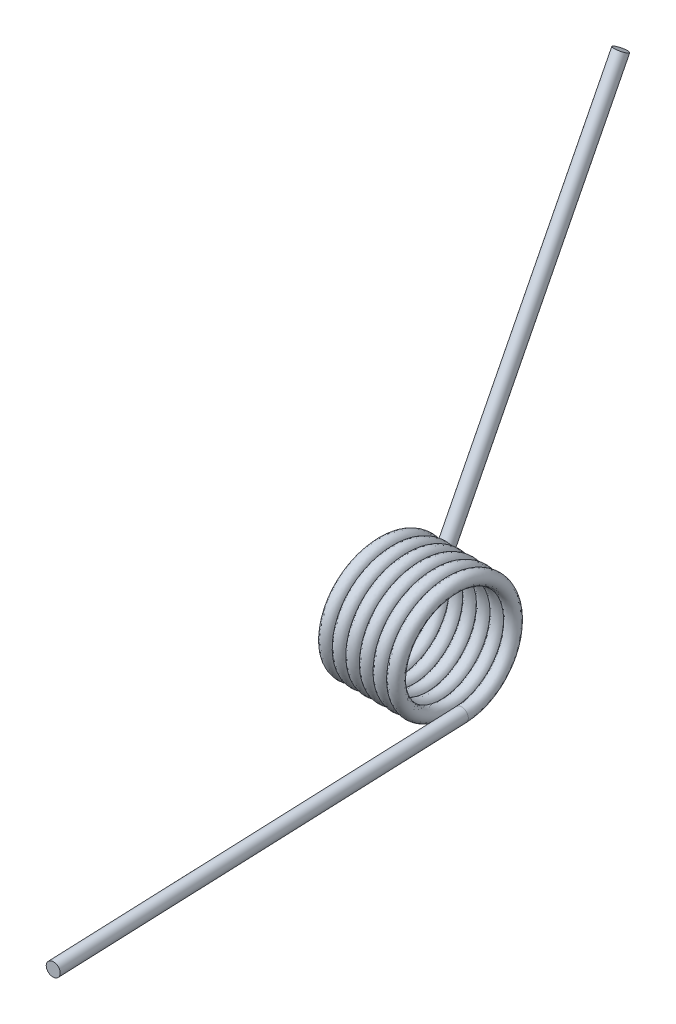
SolidWorks part; units mm, degrees
ref_plane "Front" through (0, 0, 0) normal (0, 0, 1) x (1, 0, 0)
ref_plane "Top" through (0, 0, 0) normal (0, 1, 0) x (1, 0, 0)
ref_plane "Right" through (0, 0, 0) normal (1, 0, 0) x (0, 0, -1)
sketch "Sketch1" plane through (0, 0, 0) normal (1, 0, 0) x (0, 0, -1)
  line L0 (0, -8.6487) -> (0, -11.0617) construction
  line L1 (9.5797, -5.5309) -> (47.6797, 60.4603) construction
  line L2 (0, -11.0617) -> (-76.2, -11.0617) construction
  line L3 (0, 0) -> (11.0617, 0) construction
  line L4 (0, 0) -> (9.5797, -5.5309) construction
  line L5 (-76.2, -11.0617) -> (-76.2, -8.6487) construction
  line L6 (-76.2, -8.6487) -> (0, -8.6487) construction
  line L7 (47.6797, 60.4603) -> (45.59, 61.6668) construction
  line L8 (45.59, 61.6668) -> (7.49, -4.3244) construction
  circle A0 centre (0, 0) radius 11.0617 construction
  circle A1 centre (0, 0) radius 7.9375 construction
  circle A2 centre (0, 0) radius 9.8552 construction
  point P7 (0, -9.8552)
  point P10 (0, 11.0617)
  dimension "OD" = 22.1234
  dimension "For Shaft Diameter" = 15.875
  dimension "Wire Diameter" = 2.413
  dimension "Leg Length" = 76.2
  dimension "Deflection Angle" = 120
sketch "Sketch2" plane through (0, 0, 0) normal (1, 0, 0) x (0, 0, -1)
  circle A0 centre (0, 0) radius 9.8552 construction
  circle A2 centre (0, 0) radius 9.8552
curve "Helix/Spiral1" pitch 2.4384 height 15.0368 radius 9.8552 left hand yes centre (0, 0, 0) axis (-1, 0, 0) start towards (0, 0, -1)
ref_plane "Plane1" through (0, -9.8552, 0) normal (-0.0393, 0, -0.9992) x (0.999, -0.0232, -0.0393)
sketch "Sketch3" plane through (0, -9.8552, 0) normal (-0.0393, 0, -0.9992) x (0.999, -0.0232, -0.0393)
  circle A0 centre (0, 0) radius 1.2065
  dimension "D1" = 2.413
sweep "Sweep1" add profiles "Sketch3" path "Helix/Spiral1"
sketch "Sketch4" plane through (0, 0, 0) normal (0.0393, 0, 0.9992) x (-0.999, 0.0232, 0.0393)
  circle A1 centre (-0.229, 9.8525) radius 1.2065
  circle A2 centre (-0.229, 9.8525) radius 1.2065
  dimension "D1" = 0
extrude "Extrude1" add sketch "Sketch4" along normal blind 76.2
sketch "Sketch5" plane through (-0.0233, 0.512, -0.2956) normal (-0.0393, 0.8654, -0.4996) x (0.9992, 0.0341, -0.0196)
  circle A1 centre (-15.0255, 9.8547) radius 1.2065
  circle A2 centre (-15.0255, 9.8547) radius 1.2065
  dimension "D1" = 0
extrude "Extrude2" add sketch "Sketch5" along normal blind 76.2
sketch "Sketch6" plane through (0, 0, 0) normal (1, 0, 0) x (0, 0, -1)
  circle A2 centre (0, 0) radius 8.6487 construction
equation "\"D4@Helix/Spiral1\" = \"Wire Diameter@Sketch1\" + .001"
equation "\"D1@Sketch3\"=\"Wire Diameter@Sketch1\""
equation "\"D1@Extrude2\"=\"Leg Length@Sketch1\""
equation "\"Leg Length@Extrude1\"=\"Leg Length@Sketch1\""
